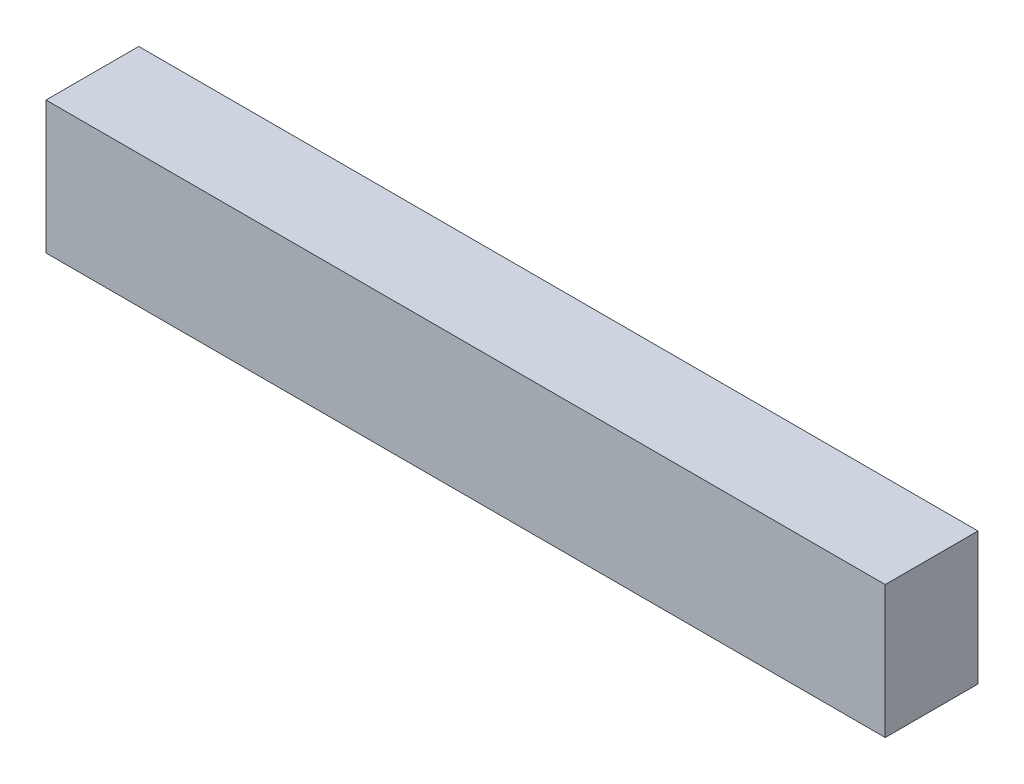
SolidWorks part; units mm, degrees
ref_plane "Front Plane" through (0, 0, 0) normal (0, 0, 1) x (1, 0, 0)
ref_plane "Top Plane" through (0, 0, 0) normal (0, 1, 0) x (1, 0, 0)
ref_plane "Right Plane" through (0, 0, 0) normal (1, 0, 0) x (0, 0, -1)
sketch "Sketch1" plane through (0, 0, 0) normal (0, 0, 1) x (1, 0, 0)
  line L1 (-34.4608, 13.5095) -> (13.7992, 13.5095)
  line L2 (-34.4608, 13.5095) -> (-34.4608, 5.8895)
  line L3 (-34.4608, 5.8895) -> (13.7992, 5.8895)
  line L4 (13.7992, 13.5095) -> (13.7992, 5.8895)
  dimension "D1" = 48.26
  dimension "D2" = 7.62
extrude "Boss-Extrude1" add sketch "Sketch1" along normal blind 5.334
equation "\"MDF\"= .21in"
equation "\"Foamcore\"= .13in"
equation "\"Gmaterial\"= \"MDF\""
equation "\"D1@Boss-Extrude1\"=\"MDF\""
